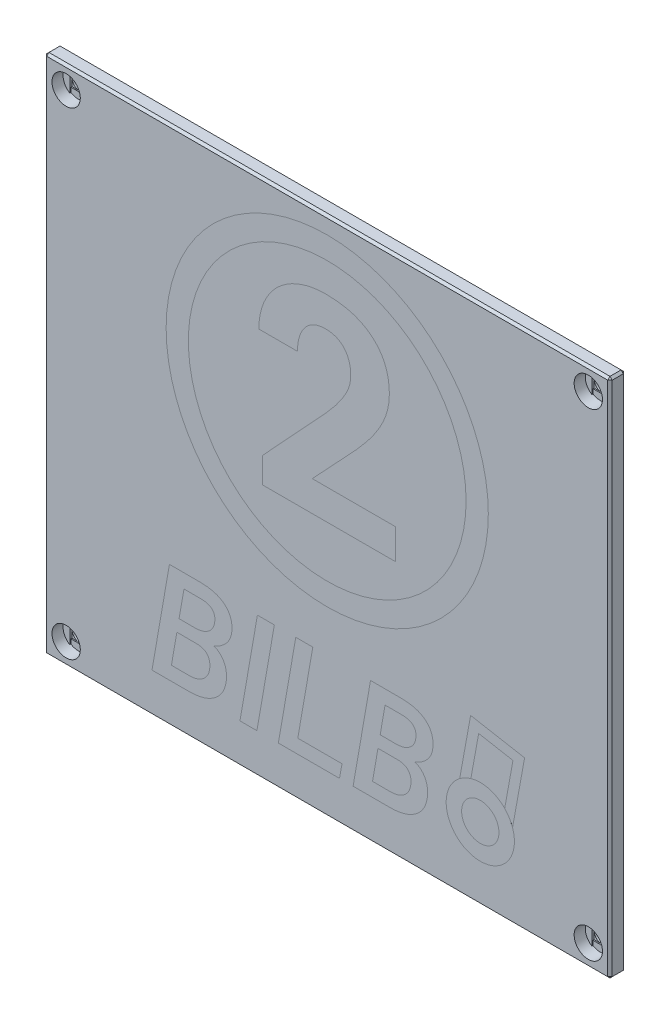
SolidWorks part; units mm, degrees
ref_plane "Front Plane" through (0, 0, 0) normal (0, 0, 1) x (1, 0, 0)
ref_plane "Top Plane" through (0, 0, 0) normal (0, 1, 0) x (1, 0, 0)
ref_plane "Right Plane" through (0, 0, 0) normal (1, 0, 0) x (0, 0, -1)
sketch "Sketch1" plane through (0, 0, 0) normal (0, 0, 1) x (1, 0, 0)
  line L0 (51, 41) -> (43, 41) construction
  line L1 (51, 33) -> (51, 41) construction
  line L2 (51, -53) -> (51, -45) construction
  line L3 (43, -53) -> (51, -53) construction
  line L4 (-51, -53) -> (-43, -53) construction
  line L5 (-51, -45) -> (-51, -53) construction
  line L6 (-51, 41) -> (-51, 33) construction
  line L7 (-43, 41) -> (-51, 41) construction
  line L8 (51, 41) -> (43, 41)
  line L9 (51, 33) -> (51, 41)
  line L10 (51, -53) -> (51, -45)
  line L11 (43, -53) -> (51, -53)
  line L12 (-51, -53) -> (-43, -53)
  line L13 (-51, -45) -> (-51, -53)
  line L14 (-51, 41) -> (-51, 33)
  line L15 (-43, 41) -> (-51, 41)
  circle A0 centre (47, 37) radius 2.15 construction
  circle A1 centre (47, -49) radius 2.15 construction
  circle A2 centre (-47, -49) radius 2.15 construction
  circle A3 centre (-47, 37) radius 2.15 construction
  circle A4 centre (47, 37) radius 2.15
  circle A5 centre (47, -49) radius 2.15
  circle A6 centre (-47, -49) radius 2.15
  circle A7 centre (-47, 37) radius 2.15
sketch "Sketch2" plane through (0, 0, 0) normal (0, 0, 1) x (1, 0, 0)
  line L0 (-51, 41) -> (-51, 33) construction
  line L1 (-50.9, 40.9) -> (50.9, 40.9)
  line L2 (-50.9, 40.9) -> (-50.9, -52.9)
  line L3 (-50.9, -52.9) -> (50.9, -52.9)
  line L4 (50.9, 40.9) -> (50.9, -52.9)
  line L5 (-43, 41) -> (-51, 41) construction
  line L6 (-51, -53) -> (-43, -53) construction
  line L7 (51, -53) -> (51, -45) construction
  circle A0 centre (-47, 37) radius 1.35
  circle A1 centre (47, 37) radius 1.35
  circle A2 centre (47, -49) radius 1.35
  circle A3 centre (-47, -49) radius 1.35
  point P12 (51, -49)
  dimension "D5" = 2.7
  dimension "D1" = 0.1
  dimension "D2" = 0.1
  dimension "D3" = 0.1
  dimension "D4" = 0.1
extrude "Boss-Extrude1" add sketch "Sketch2" along normal blind 2.8
sketch "Sketch3" plane through (0, 0, 2.8) normal (0, 0, 1) x (1, 0, 0)
  circle A0 centre (-47, 37) radius 2.55
  circle A1 centre (47, 37) radius 2.55
  circle A2 centre (47, -49) radius 2.55
  circle A3 centre (-47, -49) radius 2.55
  dimension "D1" = 5.1
extrude "Cut-Extrude1" cut sketch "Sketch3" against normal blind 2
sketch "Sketch4" plane through (0, 0, 0.8) normal (0, 0, 1) x (1, 0, 0)
  line L2 (-48.35, 34.8367) -> (-48.35, 39.1633)
  line L4 (-45.65, 34.8367) -> (-45.65, 39.1633)
  line L5 (-48.35, 34.8367) -> (-45.65, 39.1633) construction
  line L6 (-48.35, 39.1633) -> (-45.65, 34.8367) construction
  circle A0 centre (-47, 37) radius 2.55 construction
  circle A1 centre (-47, 37) radius 1.35 construction
  arc A2 (-45.65, 39.1633) -> (-48.35, 39.1633) centre (-47, 37) ccw
  arc A3 (-48.35, 34.8367) -> (-45.65, 34.8367) centre (-47, 37) ccw
  point P0 (-47, 37)
extrude "Cut-Extrude2" cut sketch "Sketch4" against normal blind 0.2
sketch "Sketch5" plane through (0, 0, 0.6) normal (0, 0, 1) x (1, 0, 0)
  line L0 (-45.65, 34.8367) -> (-45.65, 39.1633) construction
  line L1 (-48.35, 35.65) -> (-45.65, 35.65)
  line L2 (-48.35, 35.65) -> (-48.35, 38.35)
  line L3 (-48.35, 38.35) -> (-45.65, 38.35)
  line L4 (-45.65, 35.65) -> (-45.65, 38.35)
  line L5 (-48.35, 35.65) -> (-45.65, 38.35) construction
  line L6 (-48.35, 38.35) -> (-45.65, 35.65) construction
  arc A0 (-48.35, 37) -> (-45.65, 37) centre (-47, 37) ccw construction
  point P0 (-47, 37)
extrude "Cut-Extrude3" cut sketch "Sketch5" against normal blind 0.2
ref_plane "Plane1" through (0, -6, 0) normal (0, 1, 0) x (1, 0, 0)
mirror "Mirror1" about plane through (0, -6, 0) normal (0, 1, 0) of "Cut-Extrude3", "Cut-Extrude2"
mirror "Mirror2" about plane through (0, 0, 0) normal (1, 0, 0) of "Mirror1"
chamfer "Chamfer1" distance 0.4 angle 45 12 edges at (-50.9, -52.9, 1.4) (50.9, -52.9, 1.4) (50.9, 40.9, 1.4) (0, 40.9, 0) (50.9, -6, 0) (0, -52.9, 0) (-50.9, -6, 0) (-50.9, 40.9, 1.4) (50.9, -6, 2.8) (0, -52.9, 2.8) (-50.9, -6, 2.8) (0, 40.9, 2.8)
sketch "Sketch6" plane through (0, 0, 0) normal (0, 0, -1) x (-1, 0, 0)
  line L0 (-50.9, -52.5) -> (-50.9, 40.5) construction
  line L1 (-40.9, 30.9) -> (40.9, 30.9)
  line L2 (-40.9, 30.9) -> (-40.9, -42.9)
  line L3 (-40.9, -42.9) -> (40.9, -42.9)
  line L4 (40.9, 30.9) -> (40.9, -42.9)
  line L5 (-50.5, 40.9) -> (50.5, 40.9) construction
  line L6 (50.9, 40.5) -> (50.9, -52.5) construction
  line L7 (50.5, -52.9) -> (-50.5, -52.9) construction
  dimension "D1" = 10
  dimension "D2" = 10
  dimension "D3" = 10
  dimension "D4" = 10
extrude "Cut-Extrude4" cut sketch "Sketch6" against normal offset from surface (1.2 mm away) 1.6 up to face at (0, -6, 2.8)
sketch "Sketch7" plane through (0, 0, 2.8) normal (0, 0, 1) x (1, 0, 0)
  line L0 (-50.5, 40.9) -> (50.5, 40.9) construction
  circle A0 centre (0, 8.9) radius 29
  circle A1 centre (0, 8.9) radius 25
  point P0 (0, 0)
  dimension "D1" = 50
  dimension "D2" = 4
  dimension "D3" = 32
extrude "Cut-Extrude5" cut sketch "Sketch7" against normal blind 1
extrude "Boss-Extrude2" add sketch "Sketch7<2>" against normal up to surface (1 mm away) separate body up to face at (25, 8.9, 1.8)
sketch "Sketch7<2>" plane through (0, 0, 2.8) normal (0, 0, 1) x (1, 0, 0) same geometry as "Sketch7"
sketch "Sketch8" plane through (0, 0, 2.8) normal (0, 0, 1) x (1, 0, 0)
  line L0 (-19.9, -6.9) -> (20.1, -6.9) construction
  line L1 (50.5, -52.9) -> (-50.5, -52.9) construction
  line L2 (-50.9, -52.5) -> (-50.9, 40.5) construction
  text T0 "2" font "Roboto" height 35
  dimension "D1" = 46
  dimension "D2" = 40
  dimension "D3" = 31
extrude "Cut-Extrude6" cut sketch "Sketch8" against normal blind 1
extrude "Boss-Extrude3" add sketch "Sketch8<2>" against normal up to surface (1 mm away) separate body up to face at (-0.4114, 9.3776, 1.8)
sketch "Sketch8<2>" plane through (0, 0, 2.8) normal (0, 0, 1) x (1, 0, 0) same geometry as "Sketch8"
sketch "Sketch9" plane through (0, 0, 2.8) normal (0, 0, 1) x (1, 0, 0)
  line L0 (25.8125, -24.1017) -> (35.5296, -25.8622)
  line L1 (35.5296, -25.8622) -> (33.3617, -37.8275)
  line L3 (23.8504, -34.9313) -> (25.8125, -24.1017)
  line L4 (-31.5437, -45.7206) -> (-28.4059, -27.6628)
  line L5 (-28.4059, -27.6628) -> (-22.8621, -27.6752)
  line L6 (-24.9209, -45.7206) -> (-31.5437, -45.7206)
  line L7 (-27.0665, -37.5723) -> (-28.0463, -43.2153)
  line L8 (-28.0463, -43.2153) -> (-24.834, -43.2277)
  line L9 (-23.3954, -37.5847) -> (-27.0665, -37.5723)
  line L10 (-26.6696, -35.2654) -> (-23.8543, -35.2778)
  line L11 (-22.6016, -30.2053) -> (-25.789, -30.1929)
  line L12 (-25.789, -30.1929) -> (-26.6696, -35.2654)
  line L13 (-12.6549, -45.7206) -> (-15.7059, -45.7206)
  line L14 (-15.7059, -45.7206) -> (-12.5681, -27.6628)
  line L15 (-12.5681, -27.6628) -> (-9.5172, -27.6628)
  line L16 (-9.5172, -27.6628) -> (-12.6549, -45.7206)
  line L17 (-5.3004, -43.2153) -> (2.662, -43.2153)
  line L18 (2.662, -43.2153) -> (2.2155, -45.7206)
  line L19 (2.2155, -45.7206) -> (-8.7978, -45.7206)
  line L20 (-8.7978, -45.7206) -> (-5.66, -27.6628)
  line L21 (-5.66, -27.6628) -> (-2.5966, -27.6628)
  line L22 (-2.5966, -27.6628) -> (-5.3004, -43.2153)
  line L23 (4.6587, -45.7206) -> (7.7965, -27.6628)
  line L24 (7.7965, -27.6628) -> (13.3404, -27.6752)
  line L25 (11.2816, -45.7206) -> (4.6587, -45.7206)
  line L26 (9.136, -37.5723) -> (8.1562, -43.2153)
  line L27 (8.1562, -43.2153) -> (11.3684, -43.2277)
  line L28 (12.8071, -37.5847) -> (9.136, -37.5723)
  line L29 (9.5329, -35.2654) -> (12.3482, -35.2778)
  line L30 (13.6008, -30.2053) -> (10.4134, -30.1929)
  line L31 (10.4134, -30.1929) -> (9.5329, -35.2654)
  spline S0 degree 3 poles (-22.8621, -27.6752) (-20.9108, -27.6835) (-19.4473, -28.1093) (-18.4716, -28.9527) knots 0 0 0 0 1 1 1 1
  spline S1 degree 3 poles (-18.4716, -28.9527) (-17.4877, -29.7877) (-17.0536, -30.9494) (-17.1694, -32.4377) knots 0 0 0 0 1 1 1 1
  spline S2 degree 3 poles (-17.1694, -32.4377) (-17.3182, -34.1906) (-18.389, -35.5094) (-20.3816, -36.3941) knots 0 0 0 0 1 1 1 1
  spline S3 degree 3 poles (-20.3816, -36.3941) (-19.6375, -36.6586) (-19.0628, -37.1423) (-18.6577, -37.8451) knots 0 0 0 0 1 1 1 1
  spline S4 degree 3 poles (-18.6577, -37.8451) (-18.2525, -38.5479) (-18.0789, -39.3872) (-18.1368, -40.3628) knots 0 0 0 0 1 1 1 1
  spline S5 degree 3 poles (-18.1368, -40.3628) (-18.2525, -42.0165) (-18.9181, -43.3228) (-20.1336, -44.2819) knots 0 0 0 0 1 1 1 1
  spline S6 degree 3 poles (-20.1336, -44.2819) (-21.3407, -45.2411) (-22.9365, -45.7206) (-24.9209, -45.7206) knots 0 0 0 0 1 1 1 1
  spline S7 degree 3 poles (-24.834, -43.2277) (-23.8667, -43.2277) (-23.044, -42.9714) (-22.366, -42.4588) knots 0 0 0 0 1 1 1 1
  spline S8 degree 3 poles (-22.366, -42.4588) (-21.688, -41.9462) (-21.287, -41.2434) (-21.163, -40.3504) knots 0 0 0 0 1 1 1 1
  spline S9 degree 3 poles (-21.163, -40.3504) (-21.0472, -39.4988) (-21.1754, -38.8332) (-21.5474, -38.3536) knots 0 0 0 0 1 1 1 1
  spline S10 degree 3 poles (-21.5474, -38.3536) (-21.9195, -37.8741) (-22.5355, -37.6178) (-23.3954, -37.5847) knots 0 0 0 0 1 1 1 1
  spline S11 degree 3 poles (-23.8543, -35.2778) (-22.8455, -35.2778) (-22.0228, -35.0381) (-21.3862, -34.5585) knots 0 0 0 0 1 1 1 1
  spline S12 degree 3 poles (-21.3862, -34.5585) (-20.7495, -34.079) (-20.3733, -33.4299) (-20.2576, -32.6113) knots 0 0 0 0 1 1 1 1
  spline S13 degree 3 poles (-20.2576, -32.6113) (-20.0509, -31.0652) (-20.8322, -30.2632) (-22.6016, -30.2053) knots 0 0 0 0 1 1 1 1
  spline S14 degree 3 poles (13.3404, -27.6752) (15.2917, -27.6835) (16.7551, -28.1093) (17.7308, -28.9527) knots 0 0 0 0 1 1 1 1
  spline S15 degree 3 poles (17.7308, -28.9527) (18.7147, -29.7877) (19.1488, -30.9494) (19.033, -32.4377) knots 0 0 0 0 1 1 1 1
  spline S16 degree 3 poles (19.033, -32.4377) (18.8842, -34.1906) (17.8135, -35.5094) (15.8208, -36.3941) knots 0 0 0 0 1 1 1 1
  spline S17 degree 3 poles (15.8208, -36.3941) (16.565, -36.6586) (17.1396, -37.1423) (17.5448, -37.8451) knots 0 0 0 0 1 1 1 1
  spline S18 degree 3 poles (17.5448, -37.8451) (17.9499, -38.5479) (18.1235, -39.3872) (18.0657, -40.3628) knots 0 0 0 0 1 1 1 1
  spline S19 degree 3 poles (18.0657, -40.3628) (17.9499, -42.0165) (17.2843, -43.3228) (16.0689, -44.2819) knots 0 0 0 0 1 1 1 1
  spline S20 degree 3 poles (16.0689, -44.2819) (14.8617, -45.2411) (13.266, -45.7206) (11.2816, -45.7206) knots 0 0 0 0 1 1 1 1
  spline S21 degree 3 poles (11.3684, -43.2277) (12.3358, -43.2277) (13.1585, -42.9714) (13.8365, -42.4588) knots 0 0 0 0 1 1 1 1
  spline S22 degree 3 poles (13.8365, -42.4588) (14.5145, -41.9462) (14.9155, -41.2434) (15.0395, -40.3504) knots 0 0 0 0 1 1 1 1
  spline S23 degree 3 poles (15.0395, -40.3504) (15.1552, -39.4988) (15.0271, -38.8332) (14.655, -38.3536) knots 0 0 0 0 1 1 1 1
  spline S24 degree 3 poles (14.655, -38.3536) (14.2829, -37.8741) (13.667, -37.6178) (12.8071, -37.5847) knots 0 0 0 0 1 1 1 1
  spline S25 degree 3 poles (12.3482, -35.2778) (13.3569, -35.2778) (14.1796, -35.0381) (14.8162, -34.5585) knots 0 0 0 0 1 1 1 1
  spline S26 degree 3 poles (14.8162, -34.5585) (15.4529, -34.079) (15.8291, -33.4299) (15.9449, -32.6113) knots 0 0 0 0 1 1 1 1
  spline S27 degree 3 poles (15.9449, -32.6113) (16.1516, -31.0652) (15.3702, -30.2632) (13.6008, -30.2053) knots 0 0 0 0 1 1 1 1
  spline S28 degree 3 poles (27.5555, -33.6879) (25.0714, -33.6879) (22.8319, -35.1843) (21.8813, -37.4793) knots 0 0 0 0 1 1 1 1
  spline S29 degree 3 poles (21.8813, -37.4793) (20.9306, -39.7743) (21.4561, -42.416) (23.2126, -44.1725) knots 0 0 0 0 1 1 1 1
  spline S30 degree 3 poles (23.2126, -44.1725) (24.9691, -45.929) (27.6108, -46.4545) (29.9058, -45.5039) knots 0 0 0 0 1 1 1 1
  spline S31 degree 3 poles (29.9058, -45.5039) (32.2008, -44.5532) (33.6972, -42.3137) (33.6972, -39.8296) knots 0 0 0 0 1 1 1 1
  spline S32 degree 3 poles (33.6972, -39.8296) (33.6972, -38.2007) (33.0502, -36.6385) (31.8984, -35.4867) knots 0 0 0 0 1 1 1 1
  spline S33 degree 3 poles (31.8984, -35.4867) (30.7466, -34.3349) (29.1844, -33.6879) (27.5555, -33.6879) knots 0 0 0 0 1 1 1 1
  spline S34 degree 3 poles (27.5555, -36.4678) (26.1958, -36.4678) (24.9699, -37.2869) (24.4496, -38.5431) knots 0 0 0 0 1 1 1 1
  spline S35 degree 3 poles (24.4496, -38.5431) (23.9292, -39.7993) (24.2168, -41.2453) (25.1783, -42.2068) knots 0 0 0 0 1 1 1 1
  spline S36 degree 3 poles (25.1783, -42.2068) (26.1398, -43.1683) (27.5858, -43.4559) (28.842, -42.9355) knots 0 0 0 0 1 1 1 1
  spline S37 degree 3 poles (28.842, -42.9355) (30.0982, -42.4152) (30.9173, -41.1893) (30.9173, -39.8296) knots 0 0 0 0 1 1 1 1
  spline S38 degree 3 poles (30.9173, -39.8296) (30.9173, -38.938) (30.5631, -38.0829) (29.9327, -37.4524) knots 0 0 0 0 1 1 1 1
  spline S39 degree 3 poles (29.9327, -37.4524) (29.3022, -36.822) (28.4471, -36.4678) (27.5555, -36.4678) knots 0 0 0 0 1 1 1 1
extrude "Cut-Extrude7" cut sketch "Sketch9" against normal blind 1 contours S6 S5 S4 S3 S2 S1 S0 L5 L4 L6 S13 S12 S11 L10 L12 L11 S10 S9 S8 S7 L8 L7 L9 | L16 L15 L14 L13 | L22 L21 L20 L19 L18 L17 | S20 S19 S18 S17 S16 S15 S14 L24 L23 L25 S27 S26 S25 L29 L31 L30 S24 S23 S22 S21 L27 L26 L28 | S32 S33 S28 S29 S30 S31 S39 S38 S37 S36 S35 S34 region at (25.6566, -34.1715, 2.8) region at (-24.3519, -36.8002, 2.8) region at (-12.6115, -36.6917, 2.8) region at (-4.5959, -38.7514, 2.8) region at (11.8506, -36.8002, 2.8)
extrude "Boss-Extrude4" add sketch "Sketch9<5>" against normal up to surface (1 mm away) separate body contours S6 S5 S4 S3 S2 S1 S0 L5 L4 L6 S13 S12 S11 L10 L12 L11 S10 S9 S8 S7 L8 L7 L9 | L16 L15 L14 L13 | L22 L21 L20 L19 L18 L17 | S20 S19 S18 S17 S16 S15 S14 L24 L23 L25 S27 S26 S25 L29 L31 L30 S24 S23 S22 S21 L27 L26 L28 | S32 S33 S28 S29 S30 S31 S39 S38 S37 S36 S35 S34 region at (25.6566, -34.1715, 2.8) region at (-24.3519, -36.8002, 2.8) region at (-12.6115, -36.6917, 2.8) region at (-4.5959, -38.7514, 2.8) region at (11.8506, -36.8002, 2.8) up to face at (-23.5308, -33.4413, 1.8)
sketch "Sketch9<5>" plane through (0, 0, 2.8) normal (0, 0, 1) x (1, 0, 0) same geometry as "Sketch9"
sketch "Sketch10" plane through (0, 0, 2.8) normal (0, 0, 1) x (1, 0, 0)
  line L0 (35.5296, -25.8622) -> (33.3617, -37.8275) construction
  line L1 (25.8125, -24.1017) -> (35.5296, -25.8622) construction
  line L2 (23.8504, -34.9313) -> (25.8125, -24.1017) construction
  line L3 (35.5296, -25.8622) -> (33.3617, -37.8275)
  line L4 (25.8125, -24.1017) -> (35.5296, -25.8622)
  line L5 (23.8504, -34.9313) -> (25.8125, -24.1017)
  line L6 (25.8619, -33.9257) -> (27.2627, -26.1938)
  line L7 (27.2627, -26.1938) -> (33.4375, -27.3125)
  line L8 (33.4375, -27.3125) -> (31.9475, -35.5365)
  spline S0 degree 3 poles (-1225.6197, 1506.0502) (982.3666, -1830.3393) (-563.3998, 1901.4091) (234.5563, -2019.0917) knots -16.994332 -16.994332 -16.994332 -16.994332 17.994449 17.994449 17.994449 17.994449 only from (33.6972, -39.8296) to (31.8984, -35.4867) construction
  spline S2 degree 3 poles (-1250.8599, -1564.1227) (1600.0832, 1244.1119) (-1760.4257, -1001.3164) (1925.0343, 557.9529) knots -11.164114 -11.164114 -11.164114 -11.164114 12.164095 12.164095 12.164095 12.164095 only from (27.5555, -33.6879) to (21.8813, -37.4793) construction
  spline S3 degree 3 poles (33.3617, -37.8275) (33.0681, -36.9761) (32.5883, -36.1919) (31.9475, -35.5365) knots 0.422315 0.422315 0.422315 0.422315 0.985683 0.985683 0.985683 0.985683
  spline S5 degree 3 poles (25.8619, -33.9257) (25.1316, -34.1352) (24.4501, -34.4778) (23.8504, -34.9313) knots 0.23448 0.23448 0.23448 0.23448 0.550361 0.550361 0.550361 0.550361
  dimension "D1" = 1.8
  dimension "D2" = 1.8
  dimension "D3" = 1.8
extrude "Cut-Extrude8" cut sketch "Sketch10" against normal blind 1
extrude "Boss-Extrude5" add sketch "Sketch10<2>" against normal up to surface (1 mm away) separate body up to face at (27.8119, -36.0325, 1.8)
sketch "Sketch10<2>" plane through (0, 0, 2.8) normal (0, 0, 1) x (1, 0, 0) same geometry as "Sketch10"
